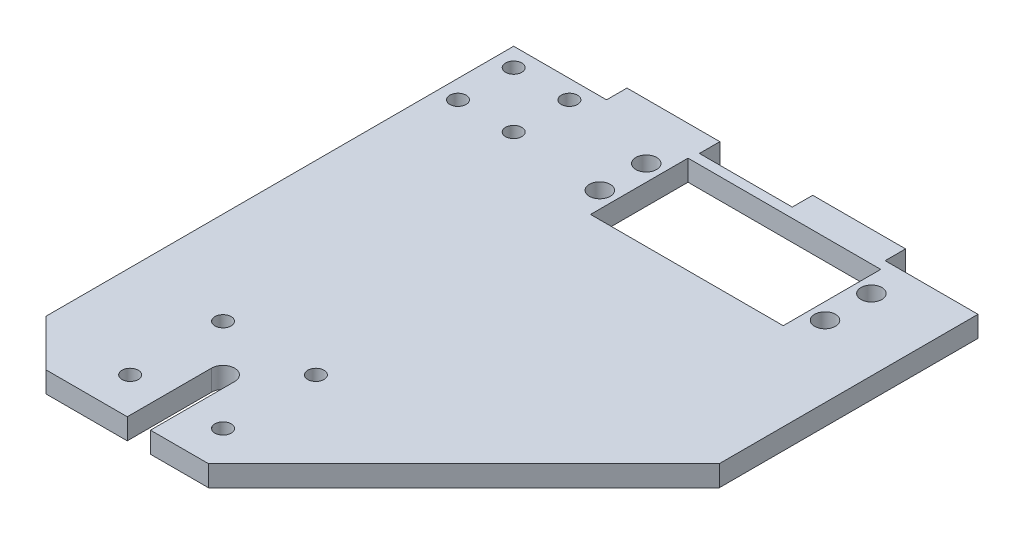
SolidWorks part; units mm, degrees
ref_plane "Front Plane" through (0, 0, 0) normal (0, 0, 1) x (1, 0, 0)
ref_plane "Top Plane" through (0, 0, 0) normal (0, 1, 0) x (1, 0, 0)
ref_plane "Right Plane" through (0, 0, 0) normal (1, 0, 0) x (0, 0, -1)
sketch "Sketch2" plane through (0, 0, 0) normal (0, 1, 0) x (1, 0, 0)
  line L3 (110, 70) -> (-110, 70)
  line L4 (110, 70) -> (110, -70)
  line L5 (110, -70) -> (-110, -70)
  line L6 (-110, 70) -> (-110, -70)
  line L7 (110, 70) -> (-110, -70) construction
  line L8 (110, -70) -> (-110, 70) construction
  point P0 (0, 0)
  dimension "D1" = 220
  dimension "D2" = 140
extrude "Boss-Extrude1" add sketch "Sketch2" along normal blind 4.5
chamfer "Chamfer1" [suppressed] distance 75 angle 40
sketch "Sketch3" plane through (0, 4.5, 0) normal (0, 1, 0) x (1, 0, 0)
  line L0 (0, 70) -> (0, -27) construction
  line L1 (110, 70) -> (-110, 70) construction
  line L2 (0, -27) -> (40.6, -27) construction
  line L3 (40.6, -27) -> (40.6, 53) construction
  line L4 (-2.5, -27) -> (-2.5, -70)
  line L5 (-110, -70) -> (110, -70) construction
  line L6 (2.5, -27) -> (2.5, -70)
  line L7 (2.5, -70) -> (-2.5, -70)
  arc A0 (2.5, -27) -> (-2.5, -27) centre (0, -27) ccw
  circle A1 centre (40.6, 53) radius 2.5
  arc A2 (-2.5, -27) -> (2.5, -27) centre (0, -27) ccw construction
  dimension "D2" = 5
  dimension "D5" = 5
  dimension "D1" = 97
  dimension "D3" = 80
  dimension "D4" = 40.6
extrude "Cut-Extrude1" cut sketch "Sketch3" against normal through all
sketch "Sketch4" plane through (0, 0, 0) normal (0, -1, 0) x (1, 0, 0)
  line L0 (110, 70) -> (110, -70) construction
  line L1 (110, -70) -> (90, -70)
  line L2 (110, -70) -> (110, -65.6)
  line L3 (110, -65.6) -> (90, -65.6)
  line L4 (90, -70) -> (90, -65.6)
  line L5 (110, -70) -> (90, -65.6) construction
  line L6 (110, -65.6) -> (90, -70) construction
  line L7 (0, -70) -> (0, 0) construction
  line L8 (70, -70) -> (50, -70)
  line L9 (70, -70) -> (70, -65.6)
  line L10 (70, -65.6) -> (50, -65.6)
  line L11 (50, -70) -> (50, -65.6)
  line L12 (70, -70) -> (50, -65.6) construction
  line L13 (70, -65.6) -> (50, -70) construction
  line L14 (30, -70) -> (10, -70)
  line L15 (30, -70) -> (30, -65.6)
  line L16 (30, -65.6) -> (10, -65.6)
  line L17 (10, -70) -> (10, -65.6)
  line L18 (30, -70) -> (10, -65.6) construction
  line L19 (30, -65.6) -> (10, -70) construction
  line L20 (-30, -65.6) -> (-10, -70) construction
  line L21 (-30, -70) -> (-10, -65.6) construction
  line L22 (-70, -65.6) -> (-50, -70) construction
  line L23 (-70, -70) -> (-50, -65.6) construction
  line L24 (-110, -65.6) -> (-90, -70) construction
  line L25 (-110, -70) -> (-90, -65.6) construction
  line L26 (-10, -70) -> (-10, -65.6)
  line L27 (-30, -65.6) -> (-10, -65.6)
  line L28 (-30, -70) -> (-30, -65.6)
  line L29 (-30, -70) -> (-10, -70)
  line L30 (-50, -70) -> (-50, -65.6)
  line L31 (-70, -65.6) -> (-50, -65.6)
  line L32 (-70, -70) -> (-70, -65.6)
  line L33 (-70, -70) -> (-50, -70)
  line L34 (-90, -70) -> (-90, -65.6)
  line L35 (-110, -65.6) -> (-90, -65.6)
  line L36 (-110, -70) -> (-110, -65.6)
  line L37 (-110, -70) -> (-90, -70)
  line L38 (0, -70) -> (110, -70) construction
  point P4 (100, -67.8)
  point P29 (-100, -67.8)
  dimension "D1" = 4.4
  dimension "D2" = 20
  dimension "D3" = 3
  dimension "D4" = 70
  dimension "D5" = 20
extrude "Teeth cut" cut sketch "Sketch4" against normal through all
sketch "Sketch5" plane through (0, 0, 0) normal (0, -1, 0) x (1, 0, 0)
  line L0 (-110, 70) -> (-2.5, 70) construction
  line L1 (110, -70.1) -> (70, -70.1)
  line L2 (110, -70.1) -> (110, 70)
  line L3 (110, 70) -> (70, 70)
  line L4 (70, -70.1) -> (70, 45.1242)
  line L5 (110, -70.1) -> (70, 70) construction
  line L6 (110, 70) -> (70, -70.1) construction
  line L7 (-110, -65.6) -> (-110, 70) construction
  line L8 (-30, -70.1) -> (-110, -70.1)
  line L9 (-30, -70.1) -> (-30, 45.1242)
  line L10 (-30, 70) -> (-110, 70)
  line L11 (-110, -70.1) -> (-110, 70)
  line L12 (-30, -70.1) -> (-110, 70) construction
  line L13 (-30, 70) -> (-110, -70.1) construction
  line L14 (110, 70) -> (110, -65.6) construction
  line L15 (-30, 45.1242) -> (-30, 70) construction
  line L16 (-30, 70) -> (70, 70)
  line L17 (-30, 70) -> (-30, 45.1242) construction
  line L18 (-30, 45.1242) -> (70, 45.1242)
  line L19 (70, 70) -> (70, 45.1242) construction
  line L20 (70, 45.1242) -> (70, 70) construction
  point P4 (90, -0.05)
  point P11 (-70, -0.05)
  dimension "D1" = 80
  dimension "D2" = 40
extrude "Trim cut" cut sketch "Sketch5" against normal through all
sketch "Sketch6" plane through (0, 4.5, 0) normal (0, 1, 0) x (1, 0, 0)
  line L0 (-30, 65.6) -> (-30, -45.1242) construction
  line L1 (51.15, 42.5) -> (9.65, 42.5)
  line L2 (51.15, 42.5) -> (51.15, 63.5)
  line L3 (51.15, 63.5) -> (9.65, 63.5)
  line L4 (9.65, 42.5) -> (9.65, 63.5)
  line L5 (51.15, 42.5) -> (9.65, 63.5) construction
  line L6 (51.15, 63.5) -> (9.65, 42.5) construction
  line L7 (-10, 65.6) -> (-30, 65.6) construction
  line L8 (-10, 65.6) -> (-10, 45.6) construction
  line L9 (-10, 45.6) -> (-30, 45.6) construction
  line L10 (-30, 65.6) -> (-30, 45.6) construction
  line L11 (-14, 61.6) -> (-26, 61.6) construction
  line L12 (-26, 61.6) -> (-26, 49.6) construction
  line L13 (-14, 49.6) -> (-26, 49.6) construction
  line L14 (-14, 61.6) -> (-14, 49.6) construction
  circle A0 centre (6.15, 58) radius 2.25
  circle A1 centre (6.15, 48) radius 2.25
  circle A2 centre (54.65, 48) radius 2.25
  circle A3 centre (54.65, 58) radius 2.25
  circle A4 centre (-14, 49.6) radius 1.75
  circle A5 centre (10, -17) radius 1.75
  circle A6 centre (10, -37) radius 1.75
  circle A7 centre (-10, -37) radius 1.75
  circle A8 centre (-10, -17) radius 1.75
  circle A9 centre (-26, 49.6) radius 1.75
  circle A10 centre (-26, 61.6) radius 1.75
  circle A11 centre (-14, 61.6) radius 1.75
  point P24 (30.4, 53)
  dimension "D1" = 4.5
  dimension "D2" = 3.5
  dimension "D3" = 21
  dimension "D4" = 41.5
  dimension "D5" = 20
  dimension "D6" = 4
extrude "Cut-Extrude2" cut sketch "Sketch6" against normal through all
ref_axis "Axis1" through (40.6, 42.5401, -53) along (0, -1, 0)
chamfer "Chamfer4" distance 10 angle 45 1 edges at (-30, 2.25, 45.1242)
chamfer "Chamfer5" distance 55 angle 45 1 edges at (70, 2.25, 45.1242)
